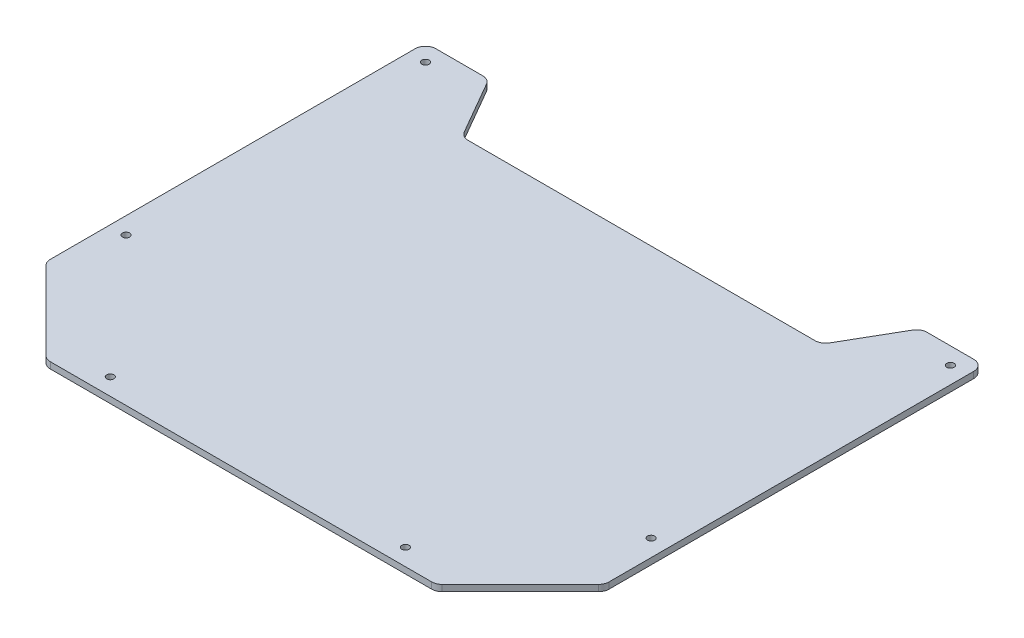
SolidWorks part; units mm, degrees
material "Acier non allié"
ref_plane "Front" through (0, 0, 0) normal (0, 0, 1) x (1, 0, 0)
ref_plane "Top" through (0, 0, 0) normal (0, 1, 0) x (1, 0, 0)
ref_plane "Right" through (0, 0, 0) normal (1, 0, 0) x (0, 0, -1)
sketch "Esquisse1" plane through (0, 0, 0) normal (0, 1, 0) x (1, 0, 0)
  line L0 (0, 0) -> (0, 1919.0564) construction
  line L1 (-92.5, 0) -> (92.5, 0)
  line L2 (92.5, 0) -> (132.5, 40)
  line L3 (132.5, 40) -> (132.5, 220)
  line L4 (132.5, 220) -> (102.5, 220)
  line L5 (102.5, 220) -> (85.1795, 190)
  line L6 (85.1795, 190) -> (-85.1795, 190)
  line L7 (-102.5, 220) -> (-85.1795, 190)
  line L8 (-132.5, 220) -> (-102.5, 220)
  line L9 (-132.5, 40) -> (-132.5, 220)
  line L10 (-92.5, 0) -> (-132.5, 40)
  point P12 (0, 190)
  dimension "D1" = 132.5
  dimension "D2" = 220
  dimension "D3" = 30
  dimension "D4" = 30
  dimension "D5" = 40
  dimension "D6" = 40
  dimension "D7" = 60
extrude "Boss.-Extru.1" add sketch "Esquisse1" along normal blind 3
fillet "Congé1" radius 5 10 edges at (132.5, 1.5, -220) (102.5, 1.5, -220) (85.1795, 1.5, -190) (-85.1795, 1.5, -190) (-102.5, 1.5, -220) (-132.5, 1.5, -220) (-132.5, 1.5, -40) (-92.5, 1.5, 0) (92.5, 1.5, 0) (132.5, 1.5, -40)
sketch "Esquisse2" plane through (0, 0, 0) normal (0, -1, 0) x (1, 0, 0)
  line L0 (0, 0) -> (0, -330.9968) construction
  line L1 (-90.4289, 0) -> (90.4289, 0) construction
  line L2 (-105.3868, -220) -> (-127.5, -220) construction
  line L3 (-132.5, -215) -> (-132.5, -42.0711) construction
  circle A0 centre (-70, -8) radius 1
  circle A1 centre (-124.5, -70) radius 1
  circle A2 centre (-124.5, -212) radius 1
  circle A3 centre (124.5, -212) radius 1
  circle A4 centre (124.5, -70) radius 1
  circle A5 centre (70, -8) radius 1
  dimension "D3" = 2
  dimension "D6" = 2
  dimension "D9" = 2
  dimension "D1" = 70
  dimension "D2" = 8
  dimension "D4" = 124.5
  dimension "D5" = 70
  dimension "D7" = 8
  dimension "D8" = 8
extrude "Enlèv. mat.-Extru.1" cut sketch "Esquisse2" against normal through all
hole_wizard "Dégagement M31" positions "Esquisse3" profile "Esquisse4" hole size "M3" standard "ISO" end condition through all
sketch "Esquisse3" plane through (0, 0, 0) normal (0, -1, 0) x (-1, 0, 0)
  point P0 (-70, 8)
  point P3 (-124.5, 70)
  point P6 (-124.5, 212)
  point P9 (124.5, 212)
  point P12 (124.5, 70)
  point P15 (70, 8)
sketch "Esquisse4" plane through (70, 0, -8) normal (1, 0, 0) x (0, 0, -1)
  line L0 (0, 0) -> (0, 3)
  line L1 (0, 3) -> (1.7, 3)
  line L2 (1.7, 3) -> (1.7, 0)
  line L5 (1.7, 0) -> (0, 0)
  line L11 (0, -6.35) -> (0, 107.95) construction
  dimension "Diamètre du perçage jusqu'au prochain" = 3.4
  dimension "Profondeur du perçage jusqu'au prochain" = 3
sketch "Esquisse5" plane through (0, 0, 0) normal (0, -1, 0) x (1, 0, 0)
  line L0 (132.5, -42.0711) -> (132.5, -215) construction
  line L1 (104.5, -82.4) -> (62.5, -82.4) construction
  line L2 (104.5, -82.4) -> (104.5, -50) construction
  line L3 (104.5, -50) -> (62.5, -50) construction
  line L4 (62.5, -82.4) -> (62.5, -50) construction
  line L5 (-90.4289, 0) -> (90.4289, 0) construction
  line L6 (83.5, -82.4) -> (83.5, -41.1293) construction
  line L7 (104.5, -66.2) -> (27.496, -66.2) construction
  line L8 (104.5, -50) -> (62.5, -50)
  line L9 (62.5, -50) -> (62.5, -62.2)
  line L10 (62.5, -62.2) -> (65.5, -63.2)
  line L11 (65.5, -63.2) -> (65.5, -69.2)
  line L12 (101.5, -63.2) -> (101.5, -69.2)
  line L13 (104.5, -62.2) -> (101.5, -63.2)
  line L14 (104.5, -50) -> (104.5, -62.2)
  line L15 (62.5, -70.2) -> (65.5, -69.2)
  line L16 (62.5, -82.4) -> (62.5, -70.2)
  line L17 (104.5, -82.4) -> (62.5, -82.4)
  line L18 (104.5, -70.2) -> (101.5, -69.2)
  line L19 (104.5, -82.4) -> (104.5, -70.2)
  point P19 (83.5, -50)
  point P21 (65.5, -66.2)
  point P23 (101.5, -66.2)
  dimension "D1" = 32.4
  dimension "D2" = 42
  dimension "D3" = 28
  dimension "D4" = 50
  dimension "D5" = 3
  dimension "D6" = 3
  dimension "D7" = 4
extrude "Enlèv. mat.-Extru.2" [suppressed] cut sketch "Esquisse5" against normal through all
equation "\"WIDTH\"= 300mm'Total width of the robot"
equation "\"LENGTH\"= 220mm'Total length of the robot"
equation "\"CUT_DEPTH\"= 45mm'Depth of the cut on the edges of the plate"
equation "\"Plate_th\"= 3mm'Thickness of the plate"
equation "\"D1\"= \"Plate_th\""
